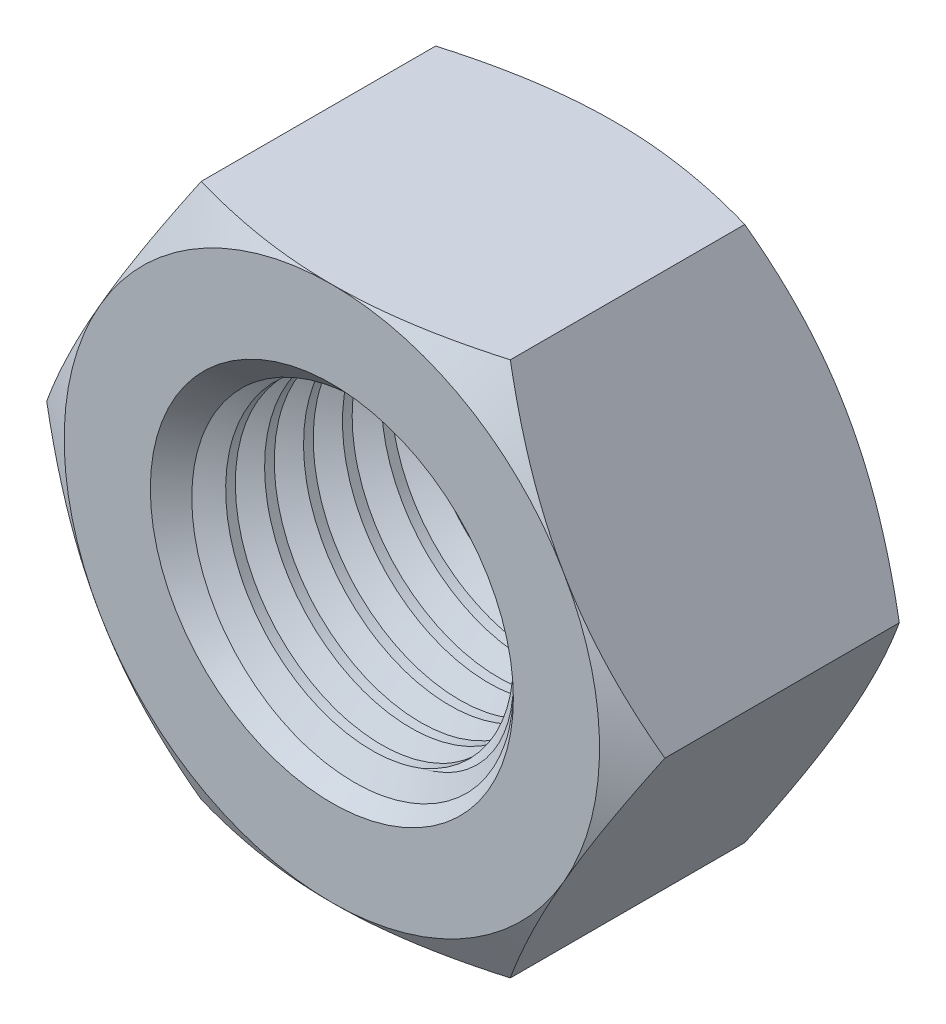
SolidWorks part; units mm, degrees
ref_plane "Front" through (0, 0, 0) normal (0, 0, 1) x (1, 0, 0)
ref_plane "Top" through (0, 0, 0) normal (0, 1, 0) x (1, 0, 0)
ref_plane "Right" through (0, 0, 0) normal (1, 0, 0) x (0, 0, -1)
sketch "Çizim1" plane through (0, 0, 0) normal (0, 0, 1) x (1, 0, 0)
  line L1 (31.7543, 0) -> (15.8771, 27.5)
  line L2 (15.8771, 27.5) -> (-15.8771, 27.5)
  line L3 (-15.8771, 27.5) -> (-31.7543, 0)
  line L4 (-31.7543, 0) -> (-15.8771, -27.5)
  line L5 (-15.8771, -27.5) -> (15.8771, -27.5)
  line L6 (15.8771, -27.5) -> (31.7543, 0)
  circle A0 centre (0, 0) radius 27.5 construction
  point P1 (0, 0)
  dimension "D1" = 55
extrude "Yükseklik-Ekstrüzyon1" add sketch "Çizim1" along normal blind 29
sketch "Çizim2" plane through (0, 0, 29) normal (0, 0, 1) x (1, 0, 0)
  circle A0 centre (0, 0) radius 27.5
extrude "Kes-Ekstrüzyon1" cut sketch "Çizim2" against normal blind 29 draft 60 flip side to cut
sketch "Çizim3" plane through (0, 0, 0) normal (0, 0, -1) x (-1, 0, 0)
  circle A0 centre (0, 0) radius 27.5
extrude "Kes-Ekstrüzyon2" cut sketch "Çizim3" against normal blind 29 draft 60 flip side to cut
sketch "Çizim4" plane through (0, 0, 29) normal (0, 0, 1) x (1, 0, 0)
  circle A0 centre (0, 0) radius 15.4
  dimension "D1" = 30.8
extrude "Kes-Ekstrüzyon3" cut sketch "Çizim4" against normal blind 29
chamfer "Pah1" distance 3.25 angle 45 2 edges at (15.4, 0, 0) (15.4, 0, 29)
sketch "Çizim5" plane through (0, 0, 0) normal (0, 0, -1) x (-1, 0, 0)
  circle A0 centre (0, 0) radius 15.4
curve "Helis/Spiral1" pitch 4 height 35 radius 15.4 centre (0, 0, 0) axis (0, 0, 1) start towards (1, 0, 0)
ref_plane "Düzlem1" through (0, -15.4, 35) normal (0.9991, 0, 0.0413) x (0.0413, 0, -0.9991)
sketch "Çizim6" plane through (0, -15.4, 35) normal (0.9991, 0, 0.0413) x (0.0413, 0, -0.9991)
  line L0 (1.9746, 0.8202) -> (-1.9746, 0.8202)
  line L1 (0, -2.6) -> (1.9746, 0.8202)
  line L3 (-1.9746, 0.8202) -> (0, -2.6)
  line L5 (0, 1.3) -> (-2.2517, 1.3) [skipped]
  circle A0 centre (0, 0) radius 1.3 construction
  dimension "D1" = 2.6
sweep "Kes-Süpür1" cut profiles "Çizim6" path "Helis/Spiral1" align with end faces yes
